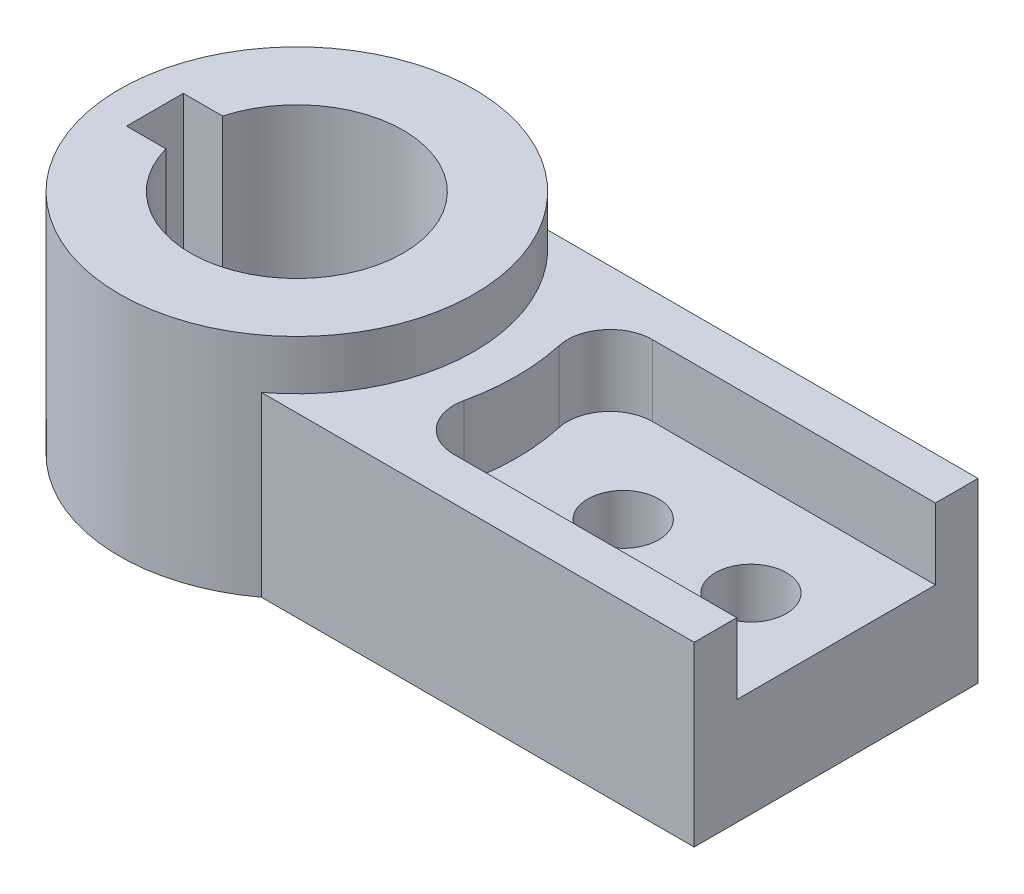
SolidWorks part; units mm, degrees
ref_plane "前视基准面" through (0, 0, 0) normal (0, 0, 1) x (1, 0, 0)
ref_plane "上视基准面" through (0, 0, 0) normal (0, 1, 0) x (1, 0, 0)
ref_plane "右视基准面" through (0, 0, 0) normal (1, 0, 0) x (0, 0, -1)
other "Configuration Table"
sketch "草图1" plane through (0, 0, 0) normal (0, 1, 0) x (1, 0, 0)
  line L0 (0, 0) -> (15, 0) construction
  line L1 (-20, 4) -> (-20, 0)
  line L2 (-20, 0) -> (-20, -4)
  line L3 (25, 0) -> (31, 0)
  line L4 (-20, 4) -> (-14.4568, 4)
  line L5 (-20, -4) -> (-14.4568, -4)
  line L6 (76, 20) -> (76, -20)
  line L7 (76, 20) -> (15, 20)
  line L8 (76, -20) -> (15, -20)
  line L9 (76, 14) -> (36.1248, 14)
  line L10 (76, -14) -> (36.1248, -14)
  line L11 (41, 0) -> (1081.3199, 0)
  arc A0 (-14.4568, -4) -> (-14.4568, 4) centre (0, 0) ccw
  circle A1 centre (0, 0) radius 25
  circle A2 centre (46, 0) radius 5
  circle A3 centre (64, 0) radius 5
  arc A5 (36.1248, -14) -> (30.2667, -6.7027) centre (36.1248, -8) cw
  arc A8 (36.1248, 14) -> (30.2667, 6.7027) centre (36.1248, 8) ccw
  arc A9 (30.2667, -6.7027) -> (30.2667, 6.7027) centre (0, 0) ccw
  point P20 (76, 0)
  point P25 (0, 0)
  point P27 (0, 0)
  point P30 (46, 0)
  point P31 (0, 0)
  dimension "D1" = 50
  dimension "D2" = 30
  dimension "D9" = 10
  dimension "D10" = 10
  dimension "D12" = 6
  dimension "D3" = 4
  dimension "D4" = 4
  dimension "D5" = 35
  dimension "D6" = 20
  dimension "D7" = 18
  dimension "D8" = 12
  dimension "D11" = 6
  dimension "D13" = 6
  dimension "D14" = 76
  dimension "D15" = 90
  dimension "D16" = 20
extrude "凸台-拉伸1" add sketch "草图1" along normal blind 32 contours A1 L1 L4 A0 L5 L2 region at (21.7282, 0, 10.8641)
extrude "凸台-拉伸2" add sketch "草图1<3>" along normal blind 25 contours A5 A9 L3 A1 L8 L6 L10 | L3 A9 A8 L9 L6 L7 A1 region at (42.5296, 0, -14.9572) region at (42.5296, 0, 14.9572)
sketch "草图1<3>" plane through (0, 0, 0) normal (0, 1, 0) x (1, 0, 0) same geometry as "草图1"
extrude "凸台-拉伸3" add sketch "草图1<4>" along normal blind 15 contours A9 A5 L10 L6 A3 A2 L9 A8 region at (31.3504, 0, -3.4298)
sketch "草图1<4>" plane through (0, 0, 0) normal (0, 1, 0) x (1, 0, 0) same geometry as "草图1"
